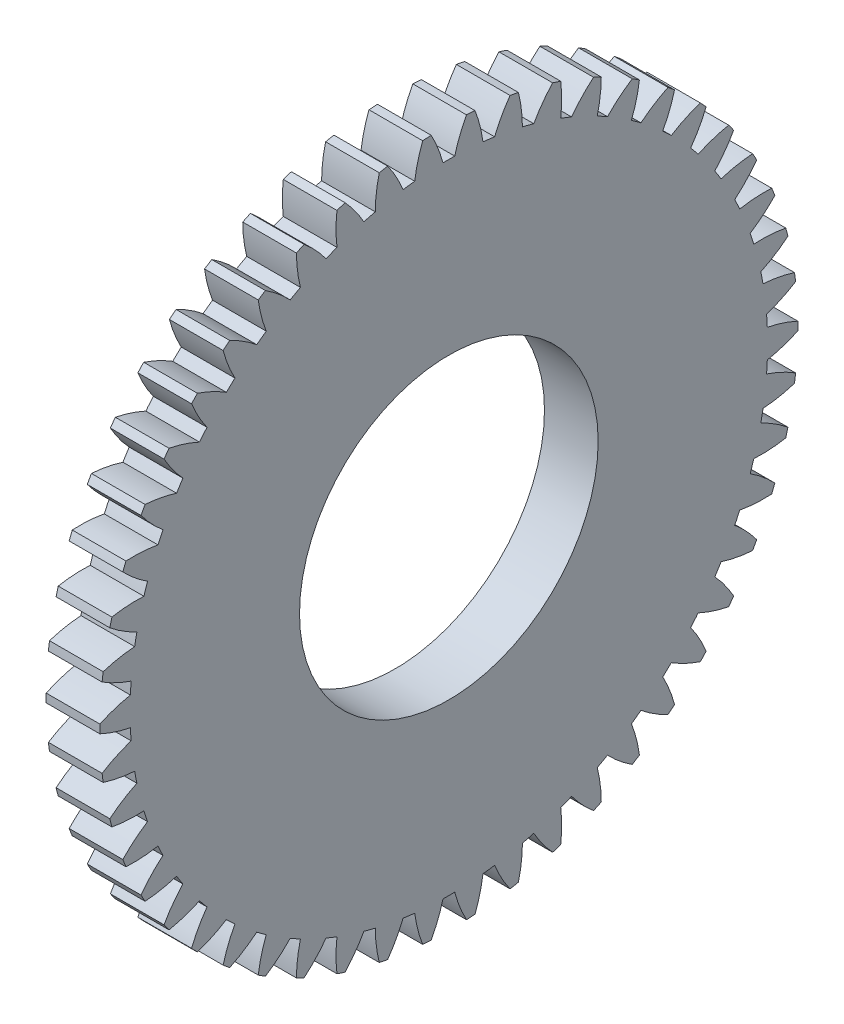
SolidWorks part; units mm, degrees
ref_plane "Plane1" through (0, 0, 0) normal (0, 0, 1) x (1, 0, 0)
ref_plane "Plane2" through (0, 0, 0) normal (0, 1, 0) x (1, 0, 0)
ref_plane "Plane3" through (0, 0, 0) normal (1, 0, 0) x (0, 0, -1)
sketch "HoldingSke" plane through (0, 0, 0) normal (0, 1, 0) x (1, 0, 0)
  line L0 (0, 0) -> (0.6428, -0.766)
  line L1 (-15, 0) -> (100, 0) construction
  line L2 (0, 0) -> (-2.1039, 2.3779)
  line L3 (0, 0) -> (-11.863, 4.5341)
  line L4 (0, 0) -> (5.5511, 6.6156)
  line L5 (0, 0) -> (-46.8476, -17.4728)
  line L6 (0, 0) -> (-3.3159, -2.2372)
  line L7 (-2.1039, 2.3779) -> (8.6586, 51.2059)
  line L8 (-76.2, 54.61) -> (-75.3, 54.61)
  line L9 (-71.009, 38.7566) -> (-53.1078, 45.2721)
  line L10 (-76.2, 71.12) -> (104.1128, 71.12)
  line L11 (0, 0) -> (-4, 0)
  line L12 (-76.2, 101.6) -> (-76.162, 101.6)
  line L13 (24.9733, 27.94) -> (52.9518, 28.4284)
  line L14 (24.9733, 27.94) -> (24.9743, 27.94)
  line L15 (24.9733, 27.94) -> (100.4006, 29.5858)
  line L16 (-63.627, -1) -> (-12.827, -1)
  circle A0 centre (0, 0) radius 2.5
  circle A1 centre (0, 0) radius 23.749
  circle A2 centre (0, 0) radius 37.5
  circle A3 centre (0, 0) radius 2.5
  dimension "MHD" = 47.498
  dimension "Hub_dia" = 75
  dimension "Bore" = 5
  dimension "MBD" = 5
  dimension "Num_teeth" = 50
  dimension "Pitch" = 1
  dimension "Overall_len" = 50
  dimension "Show_teeth" = 50
  dimension "Thickness" = 4
  dimension "OAL" = 50.0001
  dimension "T_dim" = 0.9
  dimension "Ap" = 20
  dimension "H" = 19.05
  dimension "Pitch_radius" = 180.3128
  dimension "Width" = 4
  dimension "Backlash" = 0.038
  dimension "Addendum_fac" = 1
  dimension "Dedendum_fac" = 1.25
  dimension "Clearance_fac" = 0.25
  dimension "Dedendum_add" = 0.001
  dimension "Module" = 1
sketch "BasProSke" plane through (0, 0, 0) normal (0, 1, 0) x (1, 0, 0)
  line L0 (-10, 0) -> (60, 0) construction
  line L1 (0, 0) -> (0, 26)
  line L2 (0, 0) -> (4, 0)
  line L3 (4, 0) -> (4, 26)
  line L4 (4, 26) -> (0, 26)
  dimension "Thickness" = 4
  dimension "Diameter" = 52
revolve "Base-Revolve" add sketch "BasProSke" angle 360 about L0
sketch "TooCutSke" plane through (0, 0, 0) normal (1, 0, 0) x (0, 0, -1)
  line L1 (0, 0) -> (0, 107) construction
  line L2 (0, 0) -> (-0.8518, 24.9855) construction
  line L3 (0, 0) -> (-3.1382, 49.8807) construction
  line L4 (-0.8518, 24.9855) -> (-1.5691, 24.9404) construction
  arc A0 (0.4377, 23.745) -> (-0.4377, 23.745) centre (0, 0) ccw
  arc A1 (1.3294, 25.9914) -> (-1.3294, 25.9914) centre (0, 0) ccw
  circle A2 centre (0, 0) radius 25 construction
  circle A3 centre (0, 0) radius 23.4923 construction
  arc A4 (-0.4377, 23.745) -> (-1.3294, 25.9914) centre (-10.1099, 21.2056) ccw
  arc A5 (1.3294, 25.9914) -> (0.4377, 23.745) centre (10.1099, 21.2056) ccw
  dimension "Root_dia" = 47.498
  dimension "Overcut_dia" = 52.0508
  dimension "Pitch_dia" = 50
  dimension "Base_dia" = 46.9846
  dimension "Flank_rad" = 10
  dimension "Half_ang" = 3.6
  dimension "Half_CT" = 0.7188
extrude "ToothCut" cut sketch "TooCutSke" along normal through all
fillet "Breaks" [suppressed] radius 0.02 tangent propagation no
fillet "RootFillets" [suppressed] radius 0.251
pattern_circular "TeethCuts" count 50 every 7.2 about axis through (-10, 0, 0) along (1, 0, 0) of "ToothCut", "RootFillets", "Breaks"
sketch "HubNeaOneSke" plane through (0, 0, 0) normal (-1, 0, 0) x (0, 0, 1)
  circle A0 centre (0, 0) radius 23.749
  dimension "Diameter" = 47.498
extrude "HubNearOne" [suppressed] add sketch "HubNeaOneSke" along normal blind 46.0001
sketch "HubNeaBotSke" plane through (0, 0, 0) normal (-1, 0, 0) x (0, 0, 1)
  circle A0 centre (0, 0) radius 23.749
  dimension "Diameter" = 47.498
extrude "HubNearBoth" [suppressed] add sketch "HubNeaBotSke" along normal blind 23
ref_plane "FarPln" through (4, 0, 0) normal (1, 0, 0) x (0, 0, -1)
sketch "HubFarSke" plane through (4, 0, 0) normal (1, 0, 0) x (0, 0, -1)
  circle A0 centre (0, 0) radius 23.749
  dimension "Diameter" = 47.498
extrude "HubFar" [suppressed] add sketch "HubFarSke" along normal blind 23
sketch "BorSke" plane through (0, 0, 0) normal (1, 0, 0) x (0, 0, -1)
  circle A0 centre (0, 0) radius 2.5
  dimension "Diameter" = 5
extrude "Bore" cut sketch "BorSke" along normal mid plane 100.0001
sketch "KeySke" plane through (0, 0, 0) normal (1, 0, 0) x (0, 0, -1)
  line L0 (-1, 0) -> (-1, 3.4)
  line L1 (-1, 3.4) -> (1, 3.4)
  line L2 (1, 3.4) -> (1, 0)
  line L3 (0, 0) -> (0, 34) construction
  line L4 (-1, 0) -> (1, 0)
  dimension "Offset" = 3.4
  dimension "Width" = 2
extrude "Keyway" [suppressed] cut sketch "KeySke" along normal mid plane 100.0001
pattern_circular "Keyway2" [suppressed] count 2 every 90 about axis through (-10, 0, 0) along (1, 0, 0) reverse direction yes
sketch "Sketch1" plane through (0, 0, 0) normal (-1, 0, 0) x (0, 0, 1)
  circle A0 centre (0, 0) radius 11.125
  dimension "D1" = 22.25
extrude "Cut-Extrude1" cut sketch "Sketch1" against normal up to next
equation "' \"Module@HoldingSke\" = 6.35"
equation "' \"Num_teeth@HoldingSke\" = 12"
equation "' \"Ap@HoldingSke\" =  20"
equation "' \"Ap@HoldingSke\" = 20"
equation "' \"Width@HoldingSke\" = 0.5 * 25.4"
equation "' \"Hub_dia@HoldingSke\"= 1 * 25.4"
equation "' \"Hub_dia@HoldingSke\" = 1 * 25.4"
equation "' \"Overall_len@HoldingSke\" = 1.0 * 25.4"
equation "' \"Bore@HoldingSke\" = 0.75 * 25.4"
equation "' \"T_dim@HoldingSke\" = 0.1 * 25.4"
equation "' \"Width@KeySke\" = 0.25 * 25.4"
equation "' \"Show_teeth@HoldingSke\" = 13"
equation "' \"Backlash@HoldingSke\" = 0.009 * 25.4"
equation "' \"Addendum_fac@HoldingSke\" = 1.0"
equation "' \"Dedendum_fac@HoldingSke\" = 1.25"
equation "' \"Dedendum_add@HoldingSke\" = 0.00005 * 25.4"
equation "' \"Clearance_fac@HoldingSke\" = 0.25"
equation "\"Pitch@HoldingSke\" = 1 / \"Module@HoldingSke\""
equation "\"Overcut_dia@TooCutSke\" = (\"Num_teeth@HoldingSke\" + 2 * \"Addendum_fac@HoldingSke\") / \"Pitch@HoldingSke\" + 0.002 * 25.4"
equation "\"Pitch_dia@TooCutSke\" = \"Num_teeth@HoldingSke\" / \"Pitch@HoldingSke\""
equation "\"Base_dia@TooCutSke\" = \"Num_teeth@HoldingSke\" / \"Pitch@HoldingSke\" * cos((\"Ap@HoldingSke\"  * 3.14159265 / 180))"
equation "\"Root_dia@TooCutSke\" = (\"Num_teeth@HoldingSke\" + 2) / \"Pitch@HoldingSke\" - 2 * (\"Addendum_fac@HoldingSke\" + \"Dedendum_fac@HoldingSke\") / \"Pitch@HoldingSke\" - \"Dedendum_add@HoldingSke\" * 2"
equation "\"Half_ang@TooCutSke\" = 180 / \"Num_teeth@HoldingSke\""
equation "\"Half_CT@TooCutSke\" = \"Num_teeth@HoldingSke\" / \"Pitch@HoldingSke\" * sin((3.14159265 / 2 / \"Num_teeth@HoldingSke\")) / 2 - 7 * \"Backlash@HoldingSke\" / 4"
equation "\"Flank_rad@TooCutSke\" = \"Num_teeth@HoldingSke\" / \"Pitch@HoldingSke\" / 5"
equation "\"Radius@RootFillets\" = \"Clearance_fac@HoldingSke\" / \"Pitch@HoldingSke\" + \"Dedendum_add@HoldingSke\""
equation "\"Break_rad@Breaks\" = 0.02 / \"Pitch@HoldingSke\""
equation "\"Thickness@HoldingSke\" = \"Width@HoldingSke\""
equation "\"OAL@HoldingSke\" = \"Thickness@HoldingSke\""
equation "\"MHD@HoldingSke\" = (\"Num_teeth@HoldingSke\" + 2) / \"Pitch@HoldingSke\" - 2 * (\"Addendum_fac@HoldingSke\" + \"Dedendum_fac@HoldingSke\")  / \"Pitch@HoldingSke\" - \"Dedendum_add@HoldingSke\" * 2"
equation "\"MBD@HoldingSke\" = (\"Num_teeth@HoldingSke\" + 2) / \"Pitch@HoldingSke\" - 2 * (\"Addendum_fac@HoldingSke\" + \"Dedendum_fac@HoldingSke\")  / \"Pitch@HoldingSke\" - \"Dedendum_add@HoldingSke\" * 2 - 0.002 * 25.4"
equation "\"MHD@HoldingSke\" = ((sgn( \"MHD@HoldingSke\" - \"Hub_dia@HoldingSke\" )-1)*( \"MHD@HoldingSke\" - \"Hub_dia@HoldingSke\" ))/-2+ \"Hub_dia@HoldingSke\""
equation "\"MBD@HoldingSke\" = ((sgn( \"MBD@HoldingSke\" - \"Bore@HoldingSke\" )-1)*( \"MBD@HoldingSke\" - \"Bore@HoldingSke\" ))/-2+ \"Bore@HoldingSke\""
equation "\"OAL@HoldingSke\" = ((sgn( \"OAL@HoldingSke\" - \"Overall_len@HoldingSke\" )+1)*( \"OAL@HoldingSke\" - \"Overall_len@HoldingSke\" ))/2 + \"Overall_len@HoldingSke\" + 0.000002 * 25.4"
equation "\"Num_teeth@TeethCuts\" = int( \"Show_teeth@HoldingSke\" ) + 1"
equation "\"Num_teeth@TeethCuts\" = ((sgn( \"Num_teeth@TeethCuts\" - \"Num_teeth@HoldingSke\" )-1)*( \"Num_teeth@TeethCuts\" - \"Num_teeth@HoldingSke\" ))/-2+ \"Num_teeth@HoldingSke\""
equation "\"Num_teeth@TeethCuts\" = ((sgn( \"Num_teeth@TeethCuts\" - 2.0)+1)*( \"Num_teeth@TeethCuts\" - 2.0))/2 +2.0"
equation "\"Angle@TeethCuts\" = 360.0 / \"Num_teeth@HoldingSke\""
equation "\"Diameter@BasProSke\" = (\"Num_teeth@HoldingSke\" + 2 * \"Addendum_fac@HoldingSke\") / \"Pitch@HoldingSke\""
equation "\"Thickness@BasProSke\"  = \"Thickness@HoldingSke\""
equation "' \"Fillet_rad@BasProSke\" =  \"Thickness@HoldingSke\" * 0.05"
equation "' \"Fillet_rad@BasProSke\" = \"Thickness@HoldingSke\" * 0.05"
equation "\"MHD@HoldingSke\" = ((sgn( \"MHD@HoldingSke\" - \"Root_dia@TooCutSke\" )-1)*( \"MHD@HoldingSke\" - \"Root_dia@TooCutSke\" ))/-2+ \"Root_dia@TooCutSke\""
equation "\"Diameter@HubNeaOneSke\" = \"MHD@HoldingSke\""
equation "\"Length@HubNearOne\" = \"OAL@HoldingSke\" - \"Thickness@BasProSke\""
equation "\"Diameter@HubNeaBotSke\" = \"MHD@HoldingSke\""
equation "\"Length@HubNearBoth\" = ( \"OAL@HoldingSke\" - \"Thickness@BasProSke\" ) / 2.0"
equation "\"Thickness@FarPln\" = \"Thickness@BasProSke\""
equation "\"Diameter@HubFarSke\" = \"MHD@HoldingSke\""
equation "\"Length@HubFar\" = ( \"OAL@HoldingSke\" - \"Thickness@BasProSke\" ) / 2.0"
equation "\"Diameter@BorSke\" = \"MBD@HoldingSke\""
equation "\"D1@Bore\" = \"OAL@HoldingSke\" * 2.0"
equation "\"D1@Keyway\" = \"OAL@HoldingSke\" * 2.0"
equation "\"Offset@KeySke\" = \"T_dim@HoldingSke\" + \"MBD@HoldingSke\" / 2.0"
